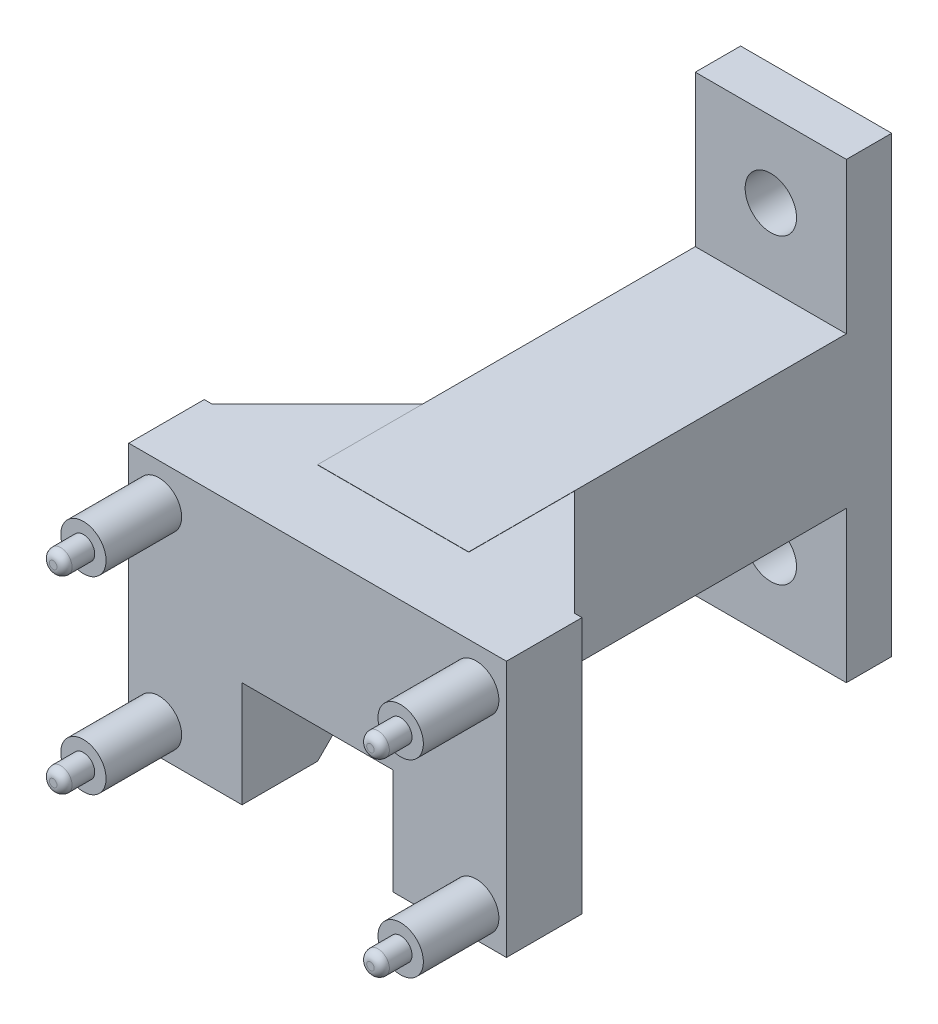
SolidWorks part; units mm, degrees
ref_plane "Front Plane" through (0, 0, 0) normal (0, 0, 1) x (1, 0, 0)
ref_plane "Top Plane" through (0, 0, 0) normal (0, 1, 0) x (1, 0, 0)
ref_plane "Right Plane" through (0, 0, 0) normal (1, 0, 0) x (0, 0, -1)
sketch "Sketch1" plane through (0, 0, 0) normal (0, 0, 1) x (1, 0, 0)
  line L1 (0, 0) -> (10, 0)
  line L2 (0, 0) -> (0, 30)
  line L3 (0, 30) -> (10, 30)
  line L4 (10, 0) -> (10, 30)
  dimension "D1" = 30
  dimension "D2" = 10
extrude "Boss-Extrude1" add sketch "Sketch1" along normal blind 3
sketch "Sketch2" plane through (0, 0, 3) normal (0, 0, 1) x (1, 0, 0)
  line L2 (10, 0) -> (10, 30) construction
  line L3 (10, 30) -> (0, 30) construction
  line L6 (0, 0) -> (10, 0) construction
  circle A3 centre (5, 25) radius 1.7
  circle A4 centre (5, 5) radius 1.7
  dimension "D1" = 5
  dimension "D2" = 5
  dimension "D5" = 3.4
  dimension "D6" = 3.4
  dimension "D3" = 5
  dimension "D4" = 5
extrude "Cut-Extrude1" cut sketch "Sketch2" against normal blind 7
sketch "Sketch3" plane through (0, 0, 3) normal (0, 0, 1) x (1, 0, 0)
  line L7 (0, 20) -> (10, 20)
  line L8 (0, 20) -> (0, 10)
  line L9 (0, 10) -> (10, 10)
  line L10 (10, 20) -> (10, 10)
  line L11 (10, 0) -> (10, 30) construction
  line L12 (0, 30) -> (0, 0) construction
  point P11 (0, 15)
  point P12 (0, 15)
  dimension "D1" = 10
extrude "Boss-Extrude2" add sketch "Sketch3" along normal blind 25
sketch "Sketch7" plane through (0, 0, 28) normal (0, 0, 1) x (1, 0, 0)
  line L0 (10, 20) -> (0, 20) construction
  line L1 (-7.5, 3) -> (17.5, 3)
  line L2 (-7.5, 3) -> (-7.5, 27)
  line L3 (-7.5, 27) -> (17.5, 27)
  line L4 (17.5, 3) -> (17.5, 27)
  line L5 (10, 0) -> (10, 30) construction
  circle A0 centre (-5.5, 5) radius 1
  circle A1 centre (15.5, 5) radius 1
  circle A2 centre (-5.5, 17.5) radius 1
  circle A3 centre (15.5, 17.5) radius 1
  point P15 (5, 20)
  point P16 (5, 27)
  point P19 (10, 15)
  point P20 (17.5, 15)
  dimension "D3" = 2
  dimension "D7" = 14.5
  dimension "D1" = 24
  dimension "D2" = 25
  dimension "D4" = 2
  dimension "D5" = 2
  dimension "D6" = 2
extrude "Boss-Extrude3" add sketch "Sketch7" along normal blind 5
sketch "Sketch9" plane through (0, 0, 28) normal (0, 0, -1) x (-1, 0, 0)
  circle A0 centre (5.5, 17.5) radius 1.5
  circle A1 centre (-15.5, 17.5) radius 1.5
  circle A2 centre (-15.5, 5) radius 1.5
  circle A3 centre (5.5, 5) radius 1.5
  dimension "D1" = 3
extrude "Boss-Extrude4" add sketch "Sketch9" against normal blind 10
sketch "Sketch10" plane through (0, 0, 38) normal (0, 0, 1) x (1, 0, 0)
  circle A0 centre (-5.5, 17.5) radius 0.75
  circle A1 centre (15.5, 17.5) radius 0.75
  circle A2 centre (15.5, 5) radius 0.75
  circle A3 centre (-5.5, 5) radius 0.75
  dimension "D1" = 1.5
extrude "Boss-Extrude5" add sketch "Sketch10" along normal blind 2
fillet "Fillet1" radius 0.5 4 edges at (16.25, 17.5, 40) (16.25, 5, 40) (-4.75, 5, 40) (-4.75, 17.5, 40)
sketch "Sketch11" plane through (0, 0, 28) normal (0, 0, -1) x (-1, 0, 0)
  line L1 (0, 30) -> (-10, 30)
  line L2 (0, 30) -> (0, 20)
  line L3 (0, 20) -> (-10, 20)
  line L4 (-10, 30) -> (-10, 20)
  line L5 (-10, 0) -> (0, 0)
  line L6 (-10, 0) -> (-10, 10)
  line L7 (-10, 10) -> (0, 10)
  line L8 (0, 0) -> (0, 10)
extrude "Cut-Extrude2" cut sketch "Sketch11" against normal blind 32
sketch "Sketch12" plane through (0, 0, 28) normal (0, 0, -1) x (-1, 0, 0)
  line L0 (7.5, 27) -> (7.5, 3) construction
  line L1 (-17.5, 27) -> (7.5, 27)
  line L2 (-17.5, 27) -> (-17.5, 19.9846)
  line L3 (-17.5, 19.9846) -> (7.5, 19.9846)
  line L4 (7.5, 27) -> (7.5, 19.9846)
extrude "Cut-Extrude3" cut sketch "Sketch12" against normal through all
chamfer "Chamfer1" distance 7 angle 45 2 edges at (10, 14.9923, 28) (0, 14.9923, 28)
chamfer "Chamfer2" distance 7 angle 45 2 edges at (13.5, 10, 28) (-3.5, 10, 28)
